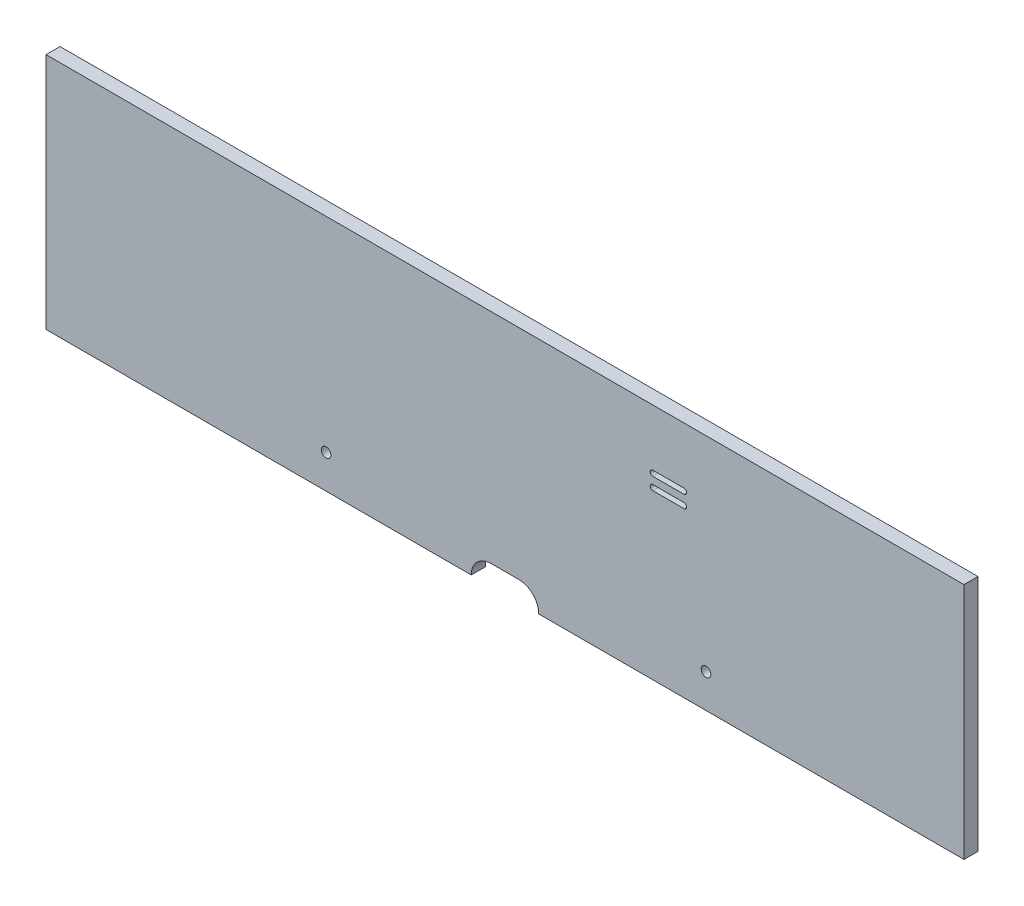
SolidWorks part; units mm, degrees
ref_plane "Front Plane" through (0, 0, 0) normal (0, 0, 1) x (1, 0, 0)
ref_plane "Top Plane" through (0, 0, 0) normal (0, 1, 0) x (1, 0, 0)
ref_plane "Right Plane" through (0, 0, 0) normal (1, 0, 0) x (0, 0, -1)
sketch "Sketch1" plane through (0, 0, 0) normal (0, 0, 1) x (1, 0, 0)
  line L1 (147.5, -38.25) -> (-147.5, -38.25)
  line L2 (147.5, -38.25) -> (147.5, 38.25)
  line L3 (147.5, 38.25) -> (-147.5, 38.25)
  line L4 (-147.5, -38.25) -> (-147.5, 38.25)
  line L5 (147.5, -38.25) -> (-147.5, 38.25) construction
  line L6 (147.5, 38.25) -> (-147.5, -38.25) construction
  point P0 (0, 0)
  dimension "D1" = 295
  dimension "D2" = 76.5
extrude "Boss-Extrude1" add sketch "Sketch1" along normal blind 4.5 contours L3 L4 L1 L2
sketch "Sketch2" plane through (0, 0, 4.5) normal (0, 0, 1) x (1, 0, 0)
  line L0 (147.5, 38.25) -> (138, 28.75) construction
  line L1 (147.5, 38.25) -> (138, 38.25) construction
  line L2 (147.5, 38.25) -> (147.5, 28.75) construction
  line L3 (147.5, 28.75) -> (138, 28.75) construction
  line L4 (138, 38.25) -> (138, 28.75) construction
  line L5 (0, 0) -> (0, -38.25) construction
  line L6 (-147.5, 38.25) -> (-138, 38.25) construction
  line L7 (-147.5, 38.25) -> (-147.5, 28.75) construction
  line L8 (-147.5, 28.75) -> (-138, 28.75) construction
  line L9 (-138, 38.25) -> (-138, 28.75) construction
  line L10 (147.5, -38.25) -> (-147.5, -38.25) construction
  line L11 (4.4678, -38.25) -> (-4.4678, -38.25) construction
  line L12 (4.4678, -44.6294) -> (-4.4678, -44.6294)
  line L13 (4.4678, -31.8706) -> (-4.4678, -31.8706)
  line L15 (-147.5, -38.25) -> (-138, -38.25) construction
  line L16 (-147.5, -38.25) -> (-147.5, -33.25) construction
  line L17 (-147.5, -33.25) -> (-138, -33.25) construction
  line L18 (-138, -38.25) -> (-138, -33.25) construction
  line L19 (147.5, -38.25) -> (138, -38.25) construction
  line L20 (147.5, -38.25) -> (147.5, -33.25) construction
  line L21 (147.5, -33.25) -> (138, -33.25) construction
  line L22 (138, -38.25) -> (138, -33.25) construction
  circle A0 centre (138, 28.75) radius 1.5 construction
  circle A1 centre (-138, 28.75) radius 1.5 construction
  arc A2 (4.4678, -44.6294) -> (4.4678, -31.8706) centre (4.4678, -38.25) ccw
  arc A3 (-4.4678, -31.8706) -> (-4.4678, -44.6294) centre (-4.4678, -38.25) ccw
  circle A4 centre (-138, -33.25) radius 1.5 construction
  circle A5 centre (138, -33.25) radius 1.5 construction
  point P19 (0, -38.25)
  point P36 (-4.4678, -38.25)
  dimension "D3" = 9.5
  dimension "D5" = 9.5
  dimension "D7" = 9.5
  dimension "D1" = 9.5
  dimension "D2" = 9.5
  dimension "D4" = 9.5
  dimension "D6" = 5
  dimension "D8" = 5
extrude "Cut-Extrude1" cut sketch "Sketch2" against normal up to next
sketch "Sketch3" plane through (0, 0, 4.5) normal (0, 0, 1) x (1, 0, 0)
  line L0 (147.5, -38.25) -> (64.6, -38.25) construction
  line L1 (147.5, -38.25) -> (10.8472, -38.25) construction
  line L2 (64.6, -38.25) -> (64.6, -27.45) construction
  line L3 (64.6, -27.45) -> (-57.5, -27.45) construction
  circle A0 centre (64.6, -27.45) radius 1.55
  circle A1 centre (-57.5, -27.45) radius 1.55
extrude "Cut-Extrude2" cut sketch "Sketch3" against normal blind 14
sketch "Sketch4" plane through (0, 0, 4.5) normal (0, 0, 1) x (1, 0, 0)
  line L0 (147.5, 38.25) -> (52.5, 38.25) construction
  line L1 (147.5, 38.25) -> (-147.5, 38.25) construction
  line L2 (52.5, 38.25) -> (52.5, 15.25) construction
  line L3 (57.5, 15.25) -> (47.5, 15.25) construction
  line L4 (57.5, 14.4) -> (47.5, 14.4)
  line L5 (57.5, 16.1) -> (47.5, 16.1)
  line L6 (57.5, 19.25) -> (47.5, 19.25) construction
  line L7 (57.5, 18.4) -> (47.5, 18.4)
  line L8 (57.5, 20.1) -> (47.5, 20.1)
  arc A0 (57.5, 14.4) -> (57.5, 16.1) centre (57.5, 15.25) ccw
  arc A1 (47.5, 16.1) -> (47.5, 14.4) centre (47.5, 15.25) ccw
  arc A2 (57.5, 18.4) -> (57.5, 20.1) centre (57.5, 19.25) ccw
  arc A3 (47.5, 20.1) -> (47.5, 18.4) centre (47.5, 19.25) ccw
  point P8 (52.5, 15.25)
  point P16 (52.5, 19.25)
  dimension "D3" = 2
  dimension "D1" = 95
  dimension "D2" = 23
extrude "Cut-Extrude3" cut sketch "Sketch4" against normal blind 8
